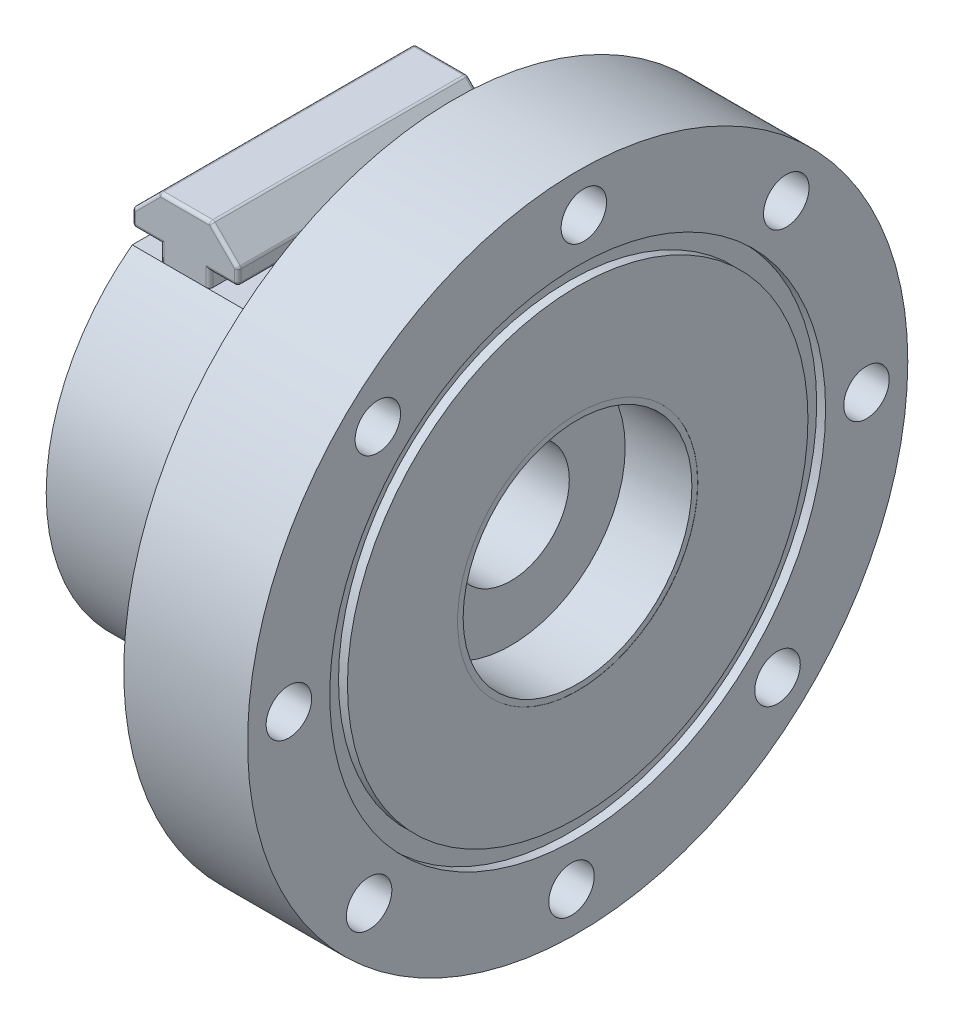
SolidWorks part; units mm, degrees
ref_plane "Front Plane" through (0, 0, 0) normal (0, 0, 1) x (1, 0, 0)
ref_plane "Top Plane" through (0, 0, 0) normal (0, 1, 0) x (1, 0, 0)
ref_plane "Right Plane" through (0, 0, 0) normal (1, 0, 0) x (0, 0, -1)
sketch "Main sketch" plane through (0, 0, 0) normal (0, 0, 1) x (1, 0, 0)
  line L0 (0, 9) -> (0, 20.075)
  line L1 (0, 20.075) -> (-8, 20.075)
  line L2 (-8, 20.075) -> (-8, 22.615)
  line L3 (-8, 33.02) -> (16.637, 33.02)
  line L4 (16.637, 33.02) -> (16.637, 50.8)
  line L5 (16.637, 50.8) -> (35.687, 50.8)
  line L6 (35.687, 50.8) -> (35.687, 38.1508)
  line L7 (35.687, 38.1508) -> (34.3154, 38.1508)
  line L8 (34.3154, 38.1508) -> (34.3154, 35.433)
  line L9 (34.3154, 35.433) -> (35.687, 35.433)
  line L10 (35.687, 35.433) -> (35.687, 18.4912)
  line L11 (35.687, 18.4912) -> (35.6616, 18.4912)
  line L12 (35.6616, 18.4912) -> (35.6616, 17.6022)
  line L13 (35.6616, 17.6022) -> (25.4, 17.6022)
  line L14 (25.4, 17.6022) -> (25.4, 9)
  line L15 (25.4, 9) -> (0, 9)
  line L16 (0, 0) -> (0, 9) construction
  line L17 (-8, 22.615) -> (-13.08, 22.615)
  line L18 (-13.08, 22.615) -> (-13.08, 33.02)
  line L19 (-13.08, 33.02) -> (-8, 33.02)
  point P20 (35.0012, 35.433)
  dimension "D1" = 9
  dimension "D2" = 20.075
  dimension "D4" = 17.6022
  dimension "D5" = 8
  dimension "D6" = 50.8
  dimension "D7" = 18.4912
  dimension "D11" = 25.4
  dimension "D12" = 10.2616
  dimension "D13" = 33.02
  dimension "D14" = 19.05
  dimension "D10" = 1.3716
  dimension "D15" = 5.08
  dimension "D16" = 2.54
  dimension "D3" = 180
  dimension "D17" = 0.0254
  dimension "D18" = 0.0254
  dimension "D8" = 38.1508
  dimension "D9" = 2.7178
ref_axis "Axis1" through (71.9501, 0, 0) along (-1, 0, 0)
revolve "Revolve1" add sketch "Main sketch" angle 360 about axis through (71.9501, 0, 0) along (-1, 0, 0)
sketch "Sketch2" plane through (35.687, 0, 0) normal (1, 0, 0) x (0, 0, -1)
  circle A0 centre (0, 0) radius 44.45 construction
  point P0 (0, 0)
  point P3 (-44.4399, 0.9486)
  point P4 (-32.0945, -30.753)
  point P7 (-0.9486, -44.4399)
  point P8 (30.753, -32.0945)
  point P9 (44.4399, -0.9486)
  point P10 (32.0945, 30.753)
  point P11 (0.9486, 44.4399)
  point P12 (-30.753, 32.0945)
  point P13 (0, 0)
  point P16 (0, 0)
  dimension "D2" = 88.9
  dimension "D1" = 8
hole_wizard "M6 Clearance Hole1" positions "Sketch2" profile "Sketch3" hole size "M6" standard "ISO" end condition through all
sketch "Sketch3" plane through (35.687, 0, 0) normal (0, 1, 0) x (0, 0, -1)
  line L0 (0, 0) -> (0, 48.767)
  line L1 (0, 48.767) -> (3.5, 48.767)
  line L2 (3.5, 48.767) -> (3.5, 0)
  line L5 (3.5, 0) -> (0, 0)
  line L11 (0, -6.35) -> (0, 107.95) construction
  dimension "Thru Hole Dia." = 7
  dimension "Thru Hole Depth" = 48.767
ref_plane "Plane1" through (0, 0, 33.02) normal (0, 0, 1) x (1, 0, 0)
ref_plane "Plane2" through (0, 33.02, 0) normal (0, 1, 0) x (1, 0, 0)
ref_plane "Plane3" through (0, 0, -33.02) normal (0, 0, -1) x (-1, 0, 0)
sketch "Sketch4" plane through (0, 33.02, 0) normal (0, 1, 0) x (1, 0, 0)
  line L0 (-13.08, -33.02) -> (16.637, -33.02) construction
  line L1 (16.637, 33.02) -> (16.637, -33.02) construction
  line L2 (16.637, 33.02) -> (-13.08, 33.02) construction
  line L4 (-13.08, -33.02) -> (16.637, -33.02)
  line L5 (16.637, 33.02) -> (16.637, -33.02)
  line L6 (16.637, 33.02) -> (-13.08, 33.02)
  line L8 (-13.08, 33.02) -> (-13.08, -33.02) construction
  line L9 (-13.08, 33.02) -> (-13.08, -33.02)
extrude "Cut-Extrude1" cut sketch "Sketch4" against normal blind 6.5786
ref_plane "Plane4" through (0, 0, -19.7781) normal (0, 0, 1) x (1, 0, 0)
ref_plane "Plane5" through (0, 0, 19.7781) normal (0, 0, -1) x (-1, 0, 0)
sketch "Sketch5" plane through (0, 0, 19.7781) normal (0, 0, -1) x (-1, 0, 0)
  line L0 (13.08, 26.4414) -> (-16.637, 26.4414) construction
  line L1 (13.08, 26.4414) -> (-16.637, 26.4414)
  line L2 (1.1912, 26.4414) -> (1.1912, 28.8684)
  line L3 (1.1912, 28.8684) -> (-3.176, 28.8684)
  line L4 (-3.176, 28.8684) -> (-3.176, 31.3274)
  line L5 (-3.176, 31.3274) -> (0.9888, 35.4922)
  line L6 (0.9888, 35.4922) -> (8.9152, 35.4922)
  line L7 (4.952, 35.4922) -> (4.952, 26.4414) construction
  line L8 (8.7128, 26.4414) -> (1.1912, 26.4414)
  line L9 (8.7128, 26.4414) -> (8.7128, 28.8684)
  line L10 (8.7128, 28.8684) -> (13.08, 28.8684)
  line L11 (13.08, 28.8684) -> (13.08, 31.3274)
  line L12 (13.08, 31.3274) -> (8.9152, 35.4922)
  line L14 (13.08, -33.02) -> (13.08, 26.4414) construction
  dimension "D1" = 3.7608
  dimension "D2" = 2.427
  dimension "D3" = 135
  dimension "D4" = 6.6238
  dimension "D5" = 8.128
  dimension "D6" = 7.9264
extrude "Boss-Extrude1" add sketch "Sketch5" along normal up to surface (39.5562 mm away) contours L7 L6 L5 L4 L3 L2 L8 | L6 L7 L1 L9 L10 L11 L12 region at (-8.2215, 31.1122, 19.7781) region at (-1.6825, 31.1122, 19.7781) up to plane "Plane4"
fillet "Fillet1" radius 0.508 24 edges at (-4.952, 35.4922, -19.7781) (-1.1912, 27.6549, 19.7781) (3.176, 30.0979, 19.7781) (0.9924, 28.8684, 19.7781) (1.0936, 33.4098, 19.7781) (-4.952, 35.4922, 19.7781) (-10.8964, 28.8684, 19.7781) (-8.7128, 27.6549, 19.7781) (-1.1912, 27.6549, -19.7781) (-8.7128, 27.6549, -19.7781) (-10.8964, 28.8684, -19.7781) (-10.9976, 33.4098, -19.7781) (-8.9152, 35.4922, 0) (-10.9976, 33.4098, 19.7781) (-13.08, 30.0979, 19.7781) (-13.08, 31.3274, 0) (-13.08, 28.8684, 0) (-13.08, 30.0979, -19.7781) (1.0936, 33.4098, -19.7781) (3.176, 30.0979, -19.7781) (0.9924, 28.8684, -19.7781) (-0.9888, 35.4922, 0) (3.176, 31.3274, 0) (3.176, 28.8684, 0)
mirror "Mirror1" about plane through (0, 0, 0) normal (0, 1, 0) of "Fillet1", "Boss-Extrude1", "Cut-Extrude1"
equation "\"Shaft_OD\"= 17mm'outer diameter of shaft"
equation "\"O_Ring_ID\"= 2.864in"
equation "\"O_Ring_CS\"= .070in'cross section"
equation "\"Bearing_OD\"= 40.15mm"
equation "\"Bearing_Depth\"= 8mm'depth bearing goes into the casing"
equation "\"Stationary_Face_Seal_OD\"= 1.386in"
equation "\"Flange_Dia\"= 4in"
equation "\"Screw_Dia\"= 6mm"
equation "\"Seal_Space\"= .3in"
equation "\"D1@Main sketch\"=\"Shaft_OD\" / 2 + .5mm"
equation "\"D2@Main sketch\" = \"Bearing_OD\" / 2"
equation "\"D4@Main sketch\" = \"Stationary_Face_Seal_OD\" / 2"
equation "\"D5@Main sketch\" = \"Bearing_Depth\""
equation "\"D6@Main sketch\" = \"Flange_Dia\" / 2"
equation "\"Seal_Area_Dia\"= 37mm"
equation "\"D7@Main sketch\"=\"Seal_space_Dia\"/2"
equation "\"Face_Seal_Height\"= 0.404in"
equation "\"D12@Main sketch\" = \"Face_Seal_Height\""
equation "\"Housing_OR\"= 1.3in'Outer radius of housing"
equation "\"D10@Main sketch\"=.054"
equation "\"D2@Sketch2\"=\"Flange_Dia\"-\"Screw_offset\""
equation "\"Screw_offset\"= .5in'offset of screws from flange OD."
equation "\"Seal_space_Dia\"= \"Stationary_Face_Seal_OD\" + .07'diameter of the space for the face seal"
equation "\"D8@Main sketch\"=(\"O_Ring_ID\"+2*\"O_Ring_CS\")/2"
equation "\"Groove_width\"=0.107"
equation "\"D9@Main sketch\"=\"Groove_width\""
